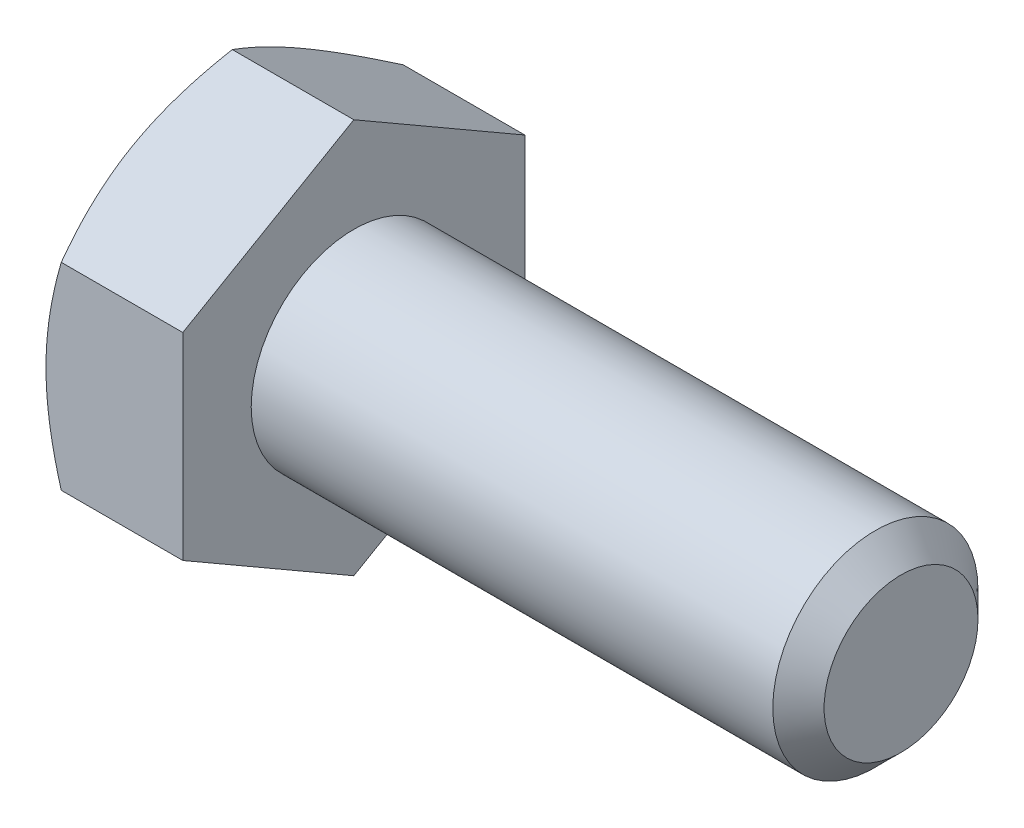
SolidWorks part; units mm, degrees
ref_plane "Front Plane" through (0, 0, 0) normal (0, 0, 1) x (1, 0, 0)
ref_plane "Top Plane" through (0, 0, 0) normal (0, 1, 0) x (1, 0, 0)
ref_plane "Right Plane" through (0, 0, 0) normal (1, 0, 0) x (0, 0, -1)
sketch "Sketch1" plane through (0, 0, 0) normal (0, 0, 1) x (1, 0, 0)
  line L0 (-10, 0) -> (10, 0) construction
  line L1 (-6, 5) -> (-6, -5) construction
  line L2 (-10, 5) -> (-10, -5) construction
  line L3 (10, 3) -> (10, -3) construction
  point P8 (6.5, -3)
  dimension "Thread Dia" = 6
  dimension "Hex" = 10
  dimension "Head Ht" = 4
  dimension "Length" = 16
  dimension "D1" = 3.5
ref_plane "Plane2" through (10, 0, 0) normal (1, 0, 0) x (0, 0, -1)
sketch "Sketch2" plane through (10, 0, 0) normal (1, 0, 0) x (0, 0, -1)
  circle A0 centre (0, 0) radius 3
extrude "Boss-Extrude1" add sketch "Sketch2" against normal up to vertex (16 mm away) up to point (-6, -5, 0)
sketch "Sketch4" plane through (10, 0, 0) normal (1, 0, 0) x (0, 0, -1)
  circle A1 centre (0, 0) radius 3
  circle A2 centre (0, 0) radius 3
  dimension "D1" = 0
curve "Helix/Spiral1" pitch 1 height 17 turns 17 parameters "Pitch"=1
chamfer "Chamfer1" distance 0.75 angle 45 1 edges at (10, 0, -3)
sketch "Sketch5" plane through (0, 0, 0) normal (0, 0, 1) x (1, 0, 0)
  line L0 (10, 3) -> (10.375, 2.3505)
  line L1 (10.375, 2.3505) -> (10.5, 2.3505)
  line L2 (10.5, 2.3505) -> (10.875, 3)
  line L3 (10, 3) -> (10.875, 3)
  line L4 (10.4375, 2.3505) -> (10.4375, 3) construction
  line L5 (10.1875, 2.6752) -> (10.6875, 2.6752) construction
  line L6 (10, -3) -> (10, 3) construction
  dimension "D1" = 60
  dimension "D2" = 0.125
  dimension "D3" = 0.5
sweep "Cut-Sweep1" [suppressed] cut profiles "Sketch5" path "Helix/Spiral1"
sketch "Sketch3" plane through (-6, 0, 0) normal (-1, 0, 0) x (0, 0, 1)
  line L0 (0, 5) -> (0, -5) construction
  line L1 (-5, -2.8868) -> (0, -5.7735)
  line L2 (0, -5.7735) -> (5, -2.8868)
  line L3 (5, -2.8868) -> (5, 2.8868)
  line L4 (5, 2.8868) -> (0, 5.7735)
  line L5 (0, 5.7735) -> (-5, 2.8868)
  line L6 (-5, 2.8868) -> (-5, -2.8868)
  circle A0 centre (0, 0) radius 5 construction
extrude "Boss-Extrude2" add sketch "Sketch3" along normal up to vertex (4 mm away) up to point (-10, -5, 0)
sketch "Sketch6" plane through (-10, 0, 0) normal (-1, 0, 0) x (0, 0, 1)
  circle A0 centre (0, 0) radius 5 construction
  circle A1 centre (0, 0) radius 5
extrude "Cut-Extrude1" cut sketch "Sketch6" against normal through all draft 60 flip side to cut
sketch "Sketch9" plane through (0, 0, 0) normal (0, 0, 1) x (1, 0, 0)
  line L0 (-6, 3) -> (-6, 0)
  line L1 (-6, 0) -> (-41, 0)
  line L2 (-41, 0) -> (-44, 3)
  line L3 (-44, 3) -> (-6, 3)
  line L4 (-10, 0) -> (10, 0) construction
  line L5 (-6, 5) -> (-6, -5) construction
  line L6 (10, 3) -> (10, -3) construction
  dimension "D1" = 45
  dimension "MinThreadLg" = 54
revolve "Revolve1" [suppressed] add sketch "Sketch9" angle 360 about L1
equation "\"D2@Sketch5\" = \"Pitch@Helix/Spiral1\"*.125"
equation "\"D3@Sketch5\" = \"Pitch@Helix/Spiral1\"*.50"
equation "\"D3@Helix/Spiral1\" = \"Length@Sketch1\"+\"Pitch@Helix/Spiral1\""
equation "\"D1@Chamfer1\" = \"Pitch@Helix/Spiral1\"*.750"
equation "\"D1@Sketch1\" = \"Pitch@Helix/Spiral1\"*3.50"
